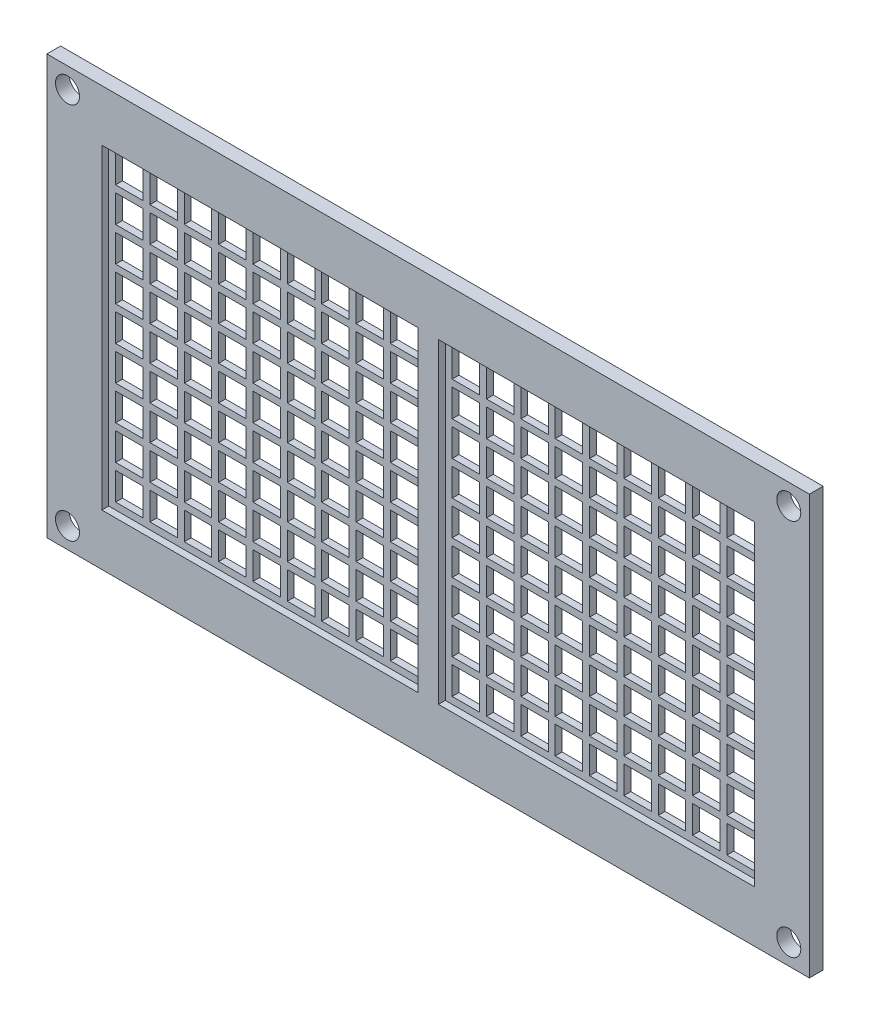
SolidWorks part; units mm, degrees
ref_plane "Front Plane" through (0, 0, 0) normal (0, 0, 1) x (1, 0, 0)
ref_plane "Top Plane" through (0, 0, 0) normal (0, 1, 0) x (1, 0, 0)
ref_plane "Right Plane" through (0, 0, 0) normal (1, 0, 0) x (0, 0, -1)
sketch "Sketch1" plane through (0, 0, 0) normal (0, 0, 1) x (1, 0, 0)
  line L1 (0, 0) -> (111, 0)
  line L2 (0, 0) -> (0, 61)
  line L3 (0, 61) -> (111, 61)
  line L4 (111, 0) -> (111, 61)
  line L5 (3, 3) -> (108, 3)
  line L6 (3, 3) -> (3, 58)
  line L7 (3, 58) -> (108, 58)
  line L8 (108, 3) -> (108, 58)
  circle A0 centre (3, 58) radius 1.75
  circle A1 centre (108, 58) radius 1.75
  circle A2 centre (108, 3) radius 1.75
  circle A3 centre (3, 3) radius 1.75
  dimension "D7" = 3.5
  dimension "D1" = 111
  dimension "D2" = 61
  dimension "D3" = 3
  dimension "D4" = 3
  dimension "D5" = 3
  dimension "D6" = 3
extrude "Boss-Extrude1" add sketch "Sketch1" along normal blind 2 contours L1 L4 L3 L2 A3 L6 A0 L7 A1 L8 A2 L5 | A3 L5 A2 L8 A1 L7 A0 L6 region at (1.2666, 30.5, 0) region at (55.5, 30.5, 0)
sketch "Sketch2" plane through (0, 0, 2) normal (0, 0, 1) x (1, 0, 0)
  line L0 (111, 0) -> (111, 61) construction
  line L1 (8, 53.5) -> (54, 53.5)
  line L2 (8, 53.5) -> (8, 7.5)
  line L3 (8, 7.5) -> (54, 7.5)
  line L4 (54, 53.5) -> (54, 7.5)
  line L5 (57, 53.5) -> (103, 53.5)
  line L6 (57, 53.5) -> (57, 7.5)
  line L7 (57, 7.5) -> (103, 7.5)
  line L8 (103, 53.5) -> (103, 7.5)
  line L9 (0, 0) -> (0, 61) construction
  line L10 (0, 61) -> (111, 61) construction
  line L11 (0, 0) -> (111, 0) construction
  dimension "D1" = 3
  dimension "D2" = 8
  dimension "D3" = 8
  dimension "D4" = 7.5
  dimension "D5" = 7.5
extrude "Cut-Extrude1" cut sketch "Sketch2" against normal blind 1
sketch "Sketch4" plane through (0, 0, 1) normal (0, 0, 1) x (1, 0, 0)
  line L0 (54, 53.5) -> (8, 53.5) construction
  line L1 (9, 52.5) -> (13, 52.5)
  line L2 (9, 52.5) -> (9, 48.5)
  line L3 (9, 48.5) -> (13, 48.5)
  line L4 (13, 52.5) -> (13, 48.5)
  line L5 (8, 53.5) -> (8, 7.5) construction
  line L6 (14, 52.5) -> (18, 52.5)
  line L7 (14, 52.5) -> (14, 48.5)
  line L8 (14, 48.5) -> (18, 48.5)
  line L9 (18, 52.5) -> (18, 48.5)
  line L10 (19, 52.5) -> (23, 52.5)
  line L11 (19, 52.5) -> (19, 48.5)
  line L12 (19, 48.5) -> (23, 48.5)
  line L13 (23, 52.5) -> (23, 48.5)
  line L14 (24, 52.5) -> (28, 52.5)
  line L15 (24, 52.5) -> (24, 48.5)
  line L16 (24, 48.5) -> (28, 48.5)
  line L17 (28, 52.5) -> (28, 48.5)
  line L18 (29, 52.5) -> (33, 52.5)
  line L19 (29, 52.5) -> (29, 48.5)
  line L20 (29, 48.5) -> (33, 48.5)
  line L21 (33, 52.5) -> (33, 48.5)
  line L22 (34, 52.5) -> (38, 52.5)
  line L23 (34, 52.5) -> (34, 48.5)
  line L24 (34, 48.5) -> (38, 48.5)
  line L25 (38, 52.5) -> (38, 48.5)
  line L26 (39, 52.5) -> (43, 52.5)
  line L27 (39, 52.5) -> (39, 48.5)
  line L28 (39, 48.5) -> (43, 48.5)
  line L29 (43, 52.5) -> (43, 48.5)
  line L30 (44, 52.5) -> (48, 52.5)
  line L31 (44, 52.5) -> (44, 48.5)
  line L32 (44, 48.5) -> (48, 48.5)
  line L33 (48, 52.5) -> (48, 48.5)
  line L34 (49, 52.5) -> (53, 52.5)
  line L35 (49, 52.5) -> (49, 48.5)
  line L36 (49, 48.5) -> (53, 48.5)
  line L37 (53, 52.5) -> (53, 48.5)
  line L38 (14, 47.5) -> (18, 47.5)
  line L39 (14, 47.5) -> (14, 43.5)
  line L40 (14, 43.5) -> (18, 43.5)
  line L41 (18, 47.5) -> (18, 43.5)
  line L42 (19, 47.5) -> (23, 47.5)
  line L43 (19, 47.5) -> (19, 43.5)
  line L44 (19, 43.5) -> (23, 43.5)
  line L45 (23, 47.5) -> (23, 43.5)
  line L46 (24, 47.5) -> (28, 47.5)
  line L47 (24, 47.5) -> (24, 43.5)
  line L48 (24, 43.5) -> (28, 43.5)
  line L49 (28, 47.5) -> (28, 43.5)
  line L50 (29, 47.5) -> (33, 47.5)
  line L51 (29, 47.5) -> (29, 43.5)
  line L52 (29, 43.5) -> (33, 43.5)
  line L53 (33, 47.5) -> (33, 43.5)
  line L54 (34, 47.5) -> (38, 47.5)
  line L55 (34, 47.5) -> (34, 43.5)
  line L56 (34, 43.5) -> (38, 43.5)
  line L57 (38, 47.5) -> (38, 43.5)
  line L58 (39, 47.5) -> (43, 47.5)
  line L59 (39, 47.5) -> (39, 43.5)
  line L60 (39, 43.5) -> (43, 43.5)
  line L61 (43, 47.5) -> (43, 43.5)
  line L62 (44, 47.5) -> (48, 47.5)
  line L63 (44, 47.5) -> (44, 43.5)
  line L64 (44, 43.5) -> (48, 43.5)
  line L65 (48, 47.5) -> (48, 43.5)
  line L66 (49, 47.5) -> (53, 47.5)
  line L67 (49, 47.5) -> (49, 43.5)
  line L68 (49, 43.5) -> (53, 43.5)
  line L69 (53, 47.5) -> (53, 43.5)
  line L70 (14, 42.5) -> (18, 42.5)
  line L71 (14, 42.5) -> (14, 38.5)
  line L72 (14, 38.5) -> (18, 38.5)
  line L73 (18, 42.5) -> (18, 38.5)
  line L74 (19, 42.5) -> (23, 42.5)
  line L75 (19, 42.5) -> (19, 38.5)
  line L76 (19, 38.5) -> (23, 38.5)
  line L77 (23, 42.5) -> (23, 38.5)
  line L78 (24, 42.5) -> (28, 42.5)
  line L79 (24, 42.5) -> (24, 38.5)
  line L80 (24, 38.5) -> (28, 38.5)
  line L81 (28, 42.5) -> (28, 38.5)
  line L82 (29, 42.5) -> (33, 42.5)
  line L83 (29, 42.5) -> (29, 38.5)
  line L84 (29, 38.5) -> (33, 38.5)
  line L85 (33, 42.5) -> (33, 38.5)
  line L86 (34, 42.5) -> (38, 42.5)
  line L87 (34, 42.5) -> (34, 38.5)
  line L88 (34, 38.5) -> (38, 38.5)
  line L89 (38, 42.5) -> (38, 38.5)
  line L90 (39, 42.5) -> (43, 42.5)
  line L91 (39, 42.5) -> (39, 38.5)
  line L92 (39, 38.5) -> (43, 38.5)
  line L93 (43, 42.5) -> (43, 38.5)
  line L94 (44, 42.5) -> (48, 42.5)
  line L95 (44, 42.5) -> (44, 38.5)
  line L96 (44, 38.5) -> (48, 38.5)
  line L97 (48, 42.5) -> (48, 38.5)
  line L98 (49, 42.5) -> (53, 42.5)
  line L99 (49, 42.5) -> (49, 38.5)
  line L100 (49, 38.5) -> (53, 38.5)
  line L101 (53, 42.5) -> (53, 38.5)
  line L102 (14, 37.5) -> (18, 37.5)
  line L103 (14, 37.5) -> (14, 33.5)
  line L104 (14, 33.5) -> (18, 33.5)
  line L105 (18, 37.5) -> (18, 33.5)
  line L106 (19, 37.5) -> (23, 37.5)
  line L107 (19, 37.5) -> (19, 33.5)
  line L108 (19, 33.5) -> (23, 33.5)
  line L109 (23, 37.5) -> (23, 33.5)
  line L110 (24, 37.5) -> (28, 37.5)
  line L111 (24, 37.5) -> (24, 33.5)
  line L112 (24, 33.5) -> (28, 33.5)
  line L113 (28, 37.5) -> (28, 33.5)
  line L114 (29, 37.5) -> (33, 37.5)
  line L115 (29, 37.5) -> (29, 33.5)
  line L116 (29, 33.5) -> (33, 33.5)
  line L117 (33, 37.5) -> (33, 33.5)
  line L118 (34, 37.5) -> (38, 37.5)
  line L119 (34, 37.5) -> (34, 33.5)
  line L120 (34, 33.5) -> (38, 33.5)
  line L121 (38, 37.5) -> (38, 33.5)
  line L122 (39, 37.5) -> (43, 37.5)
  line L123 (39, 37.5) -> (39, 33.5)
  line L124 (39, 33.5) -> (43, 33.5)
  line L125 (43, 37.5) -> (43, 33.5)
  line L126 (44, 37.5) -> (48, 37.5)
  line L127 (44, 37.5) -> (44, 33.5)
  line L128 (44, 33.5) -> (48, 33.5)
  line L129 (48, 37.5) -> (48, 33.5)
  line L130 (49, 37.5) -> (53, 37.5)
  line L131 (49, 37.5) -> (49, 33.5)
  line L132 (49, 33.5) -> (53, 33.5)
  line L133 (53, 37.5) -> (53, 33.5)
  line L134 (14, 32.5) -> (18, 32.5)
  line L135 (14, 32.5) -> (14, 28.5)
  line L136 (14, 28.5) -> (18, 28.5)
  line L137 (18, 32.5) -> (18, 28.5)
  line L138 (19, 32.5) -> (23, 32.5)
  line L139 (19, 32.5) -> (19, 28.5)
  line L140 (19, 28.5) -> (23, 28.5)
  line L141 (23, 32.5) -> (23, 28.5)
  line L142 (24, 32.5) -> (28, 32.5)
  line L143 (24, 32.5) -> (24, 28.5)
  line L144 (24, 28.5) -> (28, 28.5)
  line L145 (28, 32.5) -> (28, 28.5)
  line L146 (29, 32.5) -> (33, 32.5)
  line L147 (29, 32.5) -> (29, 28.5)
  line L148 (29, 28.5) -> (33, 28.5)
  line L149 (33, 32.5) -> (33, 28.5)
  line L150 (34, 32.5) -> (38, 32.5)
  line L151 (34, 32.5) -> (34, 28.5)
  line L152 (34, 28.5) -> (38, 28.5)
  line L153 (38, 32.5) -> (38, 28.5)
  line L154 (39, 32.5) -> (43, 32.5)
  line L155 (39, 32.5) -> (39, 28.5)
  line L156 (39, 28.5) -> (43, 28.5)
  line L157 (43, 32.5) -> (43, 28.5)
  line L158 (44, 32.5) -> (48, 32.5)
  line L159 (44, 32.5) -> (44, 28.5)
  line L160 (44, 28.5) -> (48, 28.5)
  line L161 (48, 32.5) -> (48, 28.5)
  line L162 (49, 32.5) -> (53, 32.5)
  line L163 (49, 32.5) -> (49, 28.5)
  line L164 (49, 28.5) -> (53, 28.5)
  line L165 (53, 32.5) -> (53, 28.5)
  line L166 (14, 27.5) -> (18, 27.5)
  line L167 (14, 27.5) -> (14, 23.5)
  line L168 (14, 23.5) -> (18, 23.5)
  line L169 (18, 27.5) -> (18, 23.5)
  line L170 (19, 27.5) -> (23, 27.5)
  line L171 (19, 27.5) -> (19, 23.5)
  line L172 (19, 23.5) -> (23, 23.5)
  line L173 (23, 27.5) -> (23, 23.5)
  line L174 (24, 27.5) -> (28, 27.5)
  line L175 (24, 27.5) -> (24, 23.5)
  line L176 (24, 23.5) -> (28, 23.5)
  line L177 (28, 27.5) -> (28, 23.5)
  line L178 (29, 27.5) -> (33, 27.5)
  line L179 (29, 27.5) -> (29, 23.5)
  line L180 (29, 23.5) -> (33, 23.5)
  line L181 (33, 27.5) -> (33, 23.5)
  line L182 (34, 27.5) -> (38, 27.5)
  line L183 (34, 27.5) -> (34, 23.5)
  line L184 (34, 23.5) -> (38, 23.5)
  line L185 (38, 27.5) -> (38, 23.5)
  line L186 (39, 27.5) -> (43, 27.5)
  line L187 (39, 27.5) -> (39, 23.5)
  line L188 (39, 23.5) -> (43, 23.5)
  line L189 (43, 27.5) -> (43, 23.5)
  line L190 (44, 27.5) -> (48, 27.5)
  line L191 (44, 27.5) -> (44, 23.5)
  line L192 (44, 23.5) -> (48, 23.5)
  line L193 (48, 27.5) -> (48, 23.5)
  line L194 (49, 27.5) -> (53, 27.5)
  line L195 (49, 27.5) -> (49, 23.5)
  line L196 (49, 23.5) -> (53, 23.5)
  line L197 (53, 27.5) -> (53, 23.5)
  line L198 (14, 22.5) -> (18, 22.5)
  line L199 (14, 22.5) -> (14, 18.5)
  line L200 (14, 18.5) -> (18, 18.5)
  line L201 (18, 22.5) -> (18, 18.5)
  line L202 (19, 22.5) -> (23, 22.5)
  line L203 (19, 22.5) -> (19, 18.5)
  line L204 (19, 18.5) -> (23, 18.5)
  line L205 (23, 22.5) -> (23, 18.5)
  line L206 (24, 22.5) -> (28, 22.5)
  line L207 (24, 22.5) -> (24, 18.5)
  line L208 (24, 18.5) -> (28, 18.5)
  line L209 (28, 22.5) -> (28, 18.5)
  line L210 (29, 22.5) -> (33, 22.5)
  line L211 (29, 22.5) -> (29, 18.5)
  line L212 (29, 18.5) -> (33, 18.5)
  line L213 (33, 22.5) -> (33, 18.5)
  line L214 (34, 22.5) -> (38, 22.5)
  line L215 (34, 22.5) -> (34, 18.5)
  line L216 (34, 18.5) -> (38, 18.5)
  line L217 (38, 22.5) -> (38, 18.5)
  line L218 (39, 22.5) -> (43, 22.5)
  line L219 (39, 22.5) -> (39, 18.5)
  line L220 (39, 18.5) -> (43, 18.5)
  line L221 (43, 22.5) -> (43, 18.5)
  line L222 (44, 22.5) -> (48, 22.5)
  line L223 (44, 22.5) -> (44, 18.5)
  line L224 (44, 18.5) -> (48, 18.5)
  line L225 (48, 22.5) -> (48, 18.5)
  line L226 (49, 22.5) -> (53, 22.5)
  line L227 (49, 22.5) -> (49, 18.5)
  line L228 (49, 18.5) -> (53, 18.5)
  line L229 (53, 22.5) -> (53, 18.5)
  line L230 (14, 17.5) -> (18, 17.5)
  line L231 (14, 17.5) -> (14, 13.5)
  line L232 (14, 13.5) -> (18, 13.5)
  line L233 (18, 17.5) -> (18, 13.5)
  line L234 (19, 17.5) -> (23, 17.5)
  line L235 (19, 17.5) -> (19, 13.5)
  line L236 (19, 13.5) -> (23, 13.5)
  line L237 (23, 17.5) -> (23, 13.5)
  line L238 (24, 17.5) -> (28, 17.5)
  line L239 (24, 17.5) -> (24, 13.5)
  line L240 (24, 13.5) -> (28, 13.5)
  line L241 (28, 17.5) -> (28, 13.5)
  line L242 (29, 17.5) -> (33, 17.5)
  line L243 (29, 17.5) -> (29, 13.5)
  line L244 (29, 13.5) -> (33, 13.5)
  line L245 (33, 17.5) -> (33, 13.5)
  line L246 (34, 17.5) -> (38, 17.5)
  line L247 (34, 17.5) -> (34, 13.5)
  line L248 (34, 13.5) -> (38, 13.5)
  line L249 (38, 17.5) -> (38, 13.5)
  line L250 (39, 17.5) -> (43, 17.5)
  line L251 (39, 17.5) -> (39, 13.5)
  line L252 (39, 13.5) -> (43, 13.5)
  line L253 (43, 17.5) -> (43, 13.5)
  line L254 (44, 17.5) -> (48, 17.5)
  line L255 (44, 17.5) -> (44, 13.5)
  line L256 (44, 13.5) -> (48, 13.5)
  line L257 (48, 17.5) -> (48, 13.5)
  line L258 (49, 17.5) -> (53, 17.5)
  line L259 (49, 17.5) -> (49, 13.5)
  line L260 (49, 13.5) -> (53, 13.5)
  line L261 (53, 17.5) -> (53, 13.5)
  line L262 (14, 12.5) -> (18, 12.5)
  line L263 (14, 12.5) -> (14, 8.5)
  line L264 (14, 8.5) -> (18, 8.5)
  line L265 (18, 12.5) -> (18, 8.5)
  line L266 (19, 12.5) -> (23, 12.5)
  line L267 (19, 12.5) -> (19, 8.5)
  line L268 (19, 8.5) -> (23, 8.5)
  line L269 (23, 12.5) -> (23, 8.5)
  line L270 (24, 12.5) -> (28, 12.5)
  line L271 (24, 12.5) -> (24, 8.5)
  line L272 (24, 8.5) -> (28, 8.5)
  line L273 (28, 12.5) -> (28, 8.5)
  line L274 (29, 12.5) -> (33, 12.5)
  line L275 (29, 12.5) -> (29, 8.5)
  line L276 (29, 8.5) -> (33, 8.5)
  line L277 (33, 12.5) -> (33, 8.5)
  line L278 (34, 12.5) -> (38, 12.5)
  line L279 (34, 12.5) -> (34, 8.5)
  line L280 (34, 8.5) -> (38, 8.5)
  line L281 (38, 12.5) -> (38, 8.5)
  line L282 (39, 12.5) -> (43, 12.5)
  line L283 (39, 12.5) -> (39, 8.5)
  line L284 (39, 8.5) -> (43, 8.5)
  line L285 (43, 12.5) -> (43, 8.5)
  line L286 (44, 12.5) -> (48, 12.5)
  line L287 (44, 12.5) -> (44, 8.5)
  line L288 (44, 8.5) -> (48, 8.5)
  line L289 (48, 12.5) -> (48, 8.5)
  line L290 (49, 12.5) -> (53, 12.5)
  line L291 (49, 12.5) -> (49, 8.5)
  line L292 (49, 8.5) -> (53, 8.5)
  line L293 (53, 12.5) -> (53, 8.5)
  line L294 (9, 47.5) -> (13, 47.5)
  line L295 (9, 47.5) -> (9, 43.5)
  line L296 (9, 43.5) -> (13, 43.5)
  line L297 (13, 47.5) -> (13, 43.5)
  line L298 (9, 42.5) -> (13, 42.5)
  line L299 (9, 42.5) -> (9, 38.5)
  line L300 (9, 38.5) -> (13, 38.5)
  line L301 (13, 42.5) -> (13, 38.5)
  line L302 (9, 37.5) -> (13, 37.5)
  line L303 (9, 37.5) -> (9, 33.5)
  line L304 (9, 33.5) -> (13, 33.5)
  line L305 (13, 37.5) -> (13, 33.5)
  line L306 (9, 32.5) -> (13, 32.5)
  line L307 (9, 32.5) -> (9, 28.5)
  line L308 (9, 28.5) -> (13, 28.5)
  line L309 (13, 32.5) -> (13, 28.5)
  line L310 (9, 27.5) -> (13, 27.5)
  line L311 (9, 27.5) -> (9, 23.5)
  line L312 (9, 23.5) -> (13, 23.5)
  line L313 (13, 27.5) -> (13, 23.5)
  line L314 (9, 22.5) -> (13, 22.5)
  line L315 (9, 22.5) -> (9, 18.5)
  line L316 (9, 18.5) -> (13, 18.5)
  line L317 (13, 22.5) -> (13, 18.5)
  line L318 (9, 17.5) -> (13, 17.5)
  line L319 (9, 17.5) -> (9, 13.5)
  line L320 (9, 13.5) -> (13, 13.5)
  line L321 (13, 17.5) -> (13, 13.5)
  line L322 (9, 12.5) -> (13, 12.5)
  line L323 (9, 12.5) -> (9, 8.5)
  line L324 (9, 8.5) -> (13, 8.5)
  line L325 (13, 12.5) -> (13, 8.5)
  dimension "D1" = 1
  dimension "D2" = 1
  dimension "D3" = 4
  dimension "D4" = 4
  dimension "D5" = 9
  dimension "D6" = 9
extrude "Cut-Extrude2" cut sketch "Sketch4" against normal through all
sketch "Sketch5" plane through (0, 0, 0) normal (0, 0, 1) x (1, 0, 0)
  line L1 (58, 52.5) -> (62, 52.5)
  line L2 (58, 52.5) -> (58, 48.5)
  line L3 (58, 48.5) -> (62, 48.5)
  line L4 (62, 52.5) -> (62, 48.5)
  line L6 (63, 52.5) -> (67, 52.5)
  line L7 (63, 52.5) -> (63, 48.5)
  line L8 (63, 48.5) -> (67, 48.5)
  line L9 (67, 52.5) -> (67, 48.5)
  line L10 (68, 52.5) -> (72, 52.5)
  line L11 (68, 52.5) -> (68, 48.5)
  line L12 (68, 48.5) -> (72, 48.5)
  line L13 (72, 52.5) -> (72, 48.5)
  line L14 (73, 52.5) -> (77, 52.5)
  line L15 (73, 52.5) -> (73, 48.5)
  line L16 (73, 48.5) -> (77, 48.5)
  line L17 (77, 52.5) -> (77, 48.5)
  line L18 (78, 52.5) -> (82, 52.5)
  line L19 (78, 52.5) -> (78, 48.5)
  line L20 (78, 48.5) -> (82, 48.5)
  line L21 (82, 52.5) -> (82, 48.5)
  line L22 (83, 52.5) -> (87, 52.5)
  line L23 (83, 52.5) -> (83, 48.5)
  line L24 (83, 48.5) -> (87, 48.5)
  line L25 (87, 52.5) -> (87, 48.5)
  line L26 (88, 52.5) -> (92, 52.5)
  line L27 (88, 52.5) -> (88, 48.5)
  line L28 (88, 48.5) -> (92, 48.5)
  line L29 (92, 52.5) -> (92, 48.5)
  line L30 (93, 52.5) -> (97, 52.5)
  line L31 (93, 52.5) -> (93, 48.5)
  line L32 (93, 48.5) -> (97, 48.5)
  line L33 (97, 52.5) -> (97, 48.5)
  line L34 (98, 52.5) -> (102, 52.5)
  line L35 (98, 52.5) -> (98, 48.5)
  line L36 (98, 48.5) -> (102, 48.5)
  line L37 (102, 52.5) -> (102, 48.5)
  line L38 (63, 47.5) -> (67, 47.5)
  line L39 (63, 47.5) -> (63, 43.5)
  line L40 (63, 43.5) -> (67, 43.5)
  line L41 (67, 47.5) -> (67, 43.5)
  line L42 (68, 47.5) -> (72, 47.5)
  line L43 (68, 47.5) -> (68, 43.5)
  line L44 (68, 43.5) -> (72, 43.5)
  line L45 (72, 47.5) -> (72, 43.5)
  line L46 (73, 47.5) -> (77, 47.5)
  line L47 (73, 47.5) -> (73, 43.5)
  line L48 (73, 43.5) -> (77, 43.5)
  line L49 (77, 47.5) -> (77, 43.5)
  line L50 (78, 47.5) -> (82, 47.5)
  line L51 (78, 47.5) -> (78, 43.5)
  line L52 (78, 43.5) -> (82, 43.5)
  line L53 (82, 47.5) -> (82, 43.5)
  line L54 (83, 47.5) -> (87, 47.5)
  line L55 (83, 47.5) -> (83, 43.5)
  line L56 (83, 43.5) -> (87, 43.5)
  line L57 (87, 47.5) -> (87, 43.5)
  line L58 (88, 47.5) -> (92, 47.5)
  line L59 (88, 47.5) -> (88, 43.5)
  line L60 (88, 43.5) -> (92, 43.5)
  line L61 (92, 47.5) -> (92, 43.5)
  line L62 (93, 47.5) -> (97, 47.5)
  line L63 (93, 47.5) -> (93, 43.5)
  line L64 (93, 43.5) -> (97, 43.5)
  line L65 (97, 47.5) -> (97, 43.5)
  line L66 (98, 47.5) -> (102, 47.5)
  line L67 (98, 47.5) -> (98, 43.5)
  line L68 (98, 43.5) -> (102, 43.5)
  line L69 (102, 47.5) -> (102, 43.5)
  line L70 (63, 42.5) -> (67, 42.5)
  line L71 (63, 42.5) -> (63, 38.5)
  line L72 (63, 38.5) -> (67, 38.5)
  line L73 (67, 42.5) -> (67, 38.5)
  line L74 (68, 42.5) -> (72, 42.5)
  line L75 (68, 42.5) -> (68, 38.5)
  line L76 (68, 38.5) -> (72, 38.5)
  line L77 (72, 42.5) -> (72, 38.5)
  line L78 (73, 42.5) -> (77, 42.5)
  line L79 (73, 42.5) -> (73, 38.5)
  line L80 (73, 38.5) -> (77, 38.5)
  line L81 (77, 42.5) -> (77, 38.5)
  line L82 (78, 42.5) -> (82, 42.5)
  line L83 (78, 42.5) -> (78, 38.5)
  line L84 (78, 38.5) -> (82, 38.5)
  line L85 (82, 42.5) -> (82, 38.5)
  line L86 (83, 42.5) -> (87, 42.5)
  line L87 (83, 42.5) -> (83, 38.5)
  line L88 (83, 38.5) -> (87, 38.5)
  line L89 (87, 42.5) -> (87, 38.5)
  line L90 (88, 42.5) -> (92, 42.5)
  line L91 (88, 42.5) -> (88, 38.5)
  line L92 (88, 38.5) -> (92, 38.5)
  line L93 (92, 42.5) -> (92, 38.5)
  line L94 (93, 42.5) -> (97, 42.5)
  line L95 (93, 42.5) -> (93, 38.5)
  line L96 (93, 38.5) -> (97, 38.5)
  line L97 (97, 42.5) -> (97, 38.5)
  line L98 (98, 42.5) -> (102, 42.5)
  line L99 (98, 42.5) -> (98, 38.5)
  line L100 (98, 38.5) -> (102, 38.5)
  line L101 (102, 42.5) -> (102, 38.5)
  line L102 (63, 37.5) -> (67, 37.5)
  line L103 (63, 37.5) -> (63, 33.5)
  line L104 (63, 33.5) -> (67, 33.5)
  line L105 (67, 37.5) -> (67, 33.5)
  line L106 (68, 37.5) -> (72, 37.5)
  line L107 (68, 37.5) -> (68, 33.5)
  line L108 (68, 33.5) -> (72, 33.5)
  line L109 (72, 37.5) -> (72, 33.5)
  line L110 (73, 37.5) -> (77, 37.5)
  line L111 (73, 37.5) -> (73, 33.5)
  line L112 (73, 33.5) -> (77, 33.5)
  line L113 (77, 37.5) -> (77, 33.5)
  line L114 (78, 37.5) -> (82, 37.5)
  line L115 (78, 37.5) -> (78, 33.5)
  line L116 (78, 33.5) -> (82, 33.5)
  line L117 (82, 37.5) -> (82, 33.5)
  line L118 (83, 37.5) -> (87, 37.5)
  line L119 (83, 37.5) -> (83, 33.5)
  line L120 (83, 33.5) -> (87, 33.5)
  line L121 (87, 37.5) -> (87, 33.5)
  line L122 (88, 37.5) -> (92, 37.5)
  line L123 (88, 37.5) -> (88, 33.5)
  line L124 (88, 33.5) -> (92, 33.5)
  line L125 (92, 37.5) -> (92, 33.5)
  line L126 (93, 37.5) -> (97, 37.5)
  line L127 (93, 37.5) -> (93, 33.5)
  line L128 (93, 33.5) -> (97, 33.5)
  line L129 (97, 37.5) -> (97, 33.5)
  line L130 (98, 37.5) -> (102, 37.5)
  line L131 (98, 37.5) -> (98, 33.5)
  line L132 (98, 33.5) -> (102, 33.5)
  line L133 (102, 37.5) -> (102, 33.5)
  line L134 (63, 32.5) -> (67, 32.5)
  line L135 (63, 32.5) -> (63, 28.5)
  line L136 (63, 28.5) -> (67, 28.5)
  line L137 (67, 32.5) -> (67, 28.5)
  line L138 (68, 32.5) -> (72, 32.5)
  line L139 (68, 32.5) -> (68, 28.5)
  line L140 (68, 28.5) -> (72, 28.5)
  line L141 (72, 32.5) -> (72, 28.5)
  line L142 (73, 32.5) -> (77, 32.5)
  line L143 (73, 32.5) -> (73, 28.5)
  line L144 (73, 28.5) -> (77, 28.5)
  line L145 (77, 32.5) -> (77, 28.5)
  line L146 (78, 32.5) -> (82, 32.5)
  line L147 (78, 32.5) -> (78, 28.5)
  line L148 (78, 28.5) -> (82, 28.5)
  line L149 (82, 32.5) -> (82, 28.5)
  line L150 (83, 32.5) -> (87, 32.5)
  line L151 (83, 32.5) -> (83, 28.5)
  line L152 (83, 28.5) -> (87, 28.5)
  line L153 (87, 32.5) -> (87, 28.5)
  line L154 (88, 32.5) -> (92, 32.5)
  line L155 (88, 32.5) -> (88, 28.5)
  line L156 (88, 28.5) -> (92, 28.5)
  line L157 (92, 32.5) -> (92, 28.5)
  line L158 (93, 32.5) -> (97, 32.5)
  line L159 (93, 32.5) -> (93, 28.5)
  line L160 (93, 28.5) -> (97, 28.5)
  line L161 (97, 32.5) -> (97, 28.5)
  line L162 (98, 32.5) -> (102, 32.5)
  line L163 (98, 32.5) -> (98, 28.5)
  line L164 (98, 28.5) -> (102, 28.5)
  line L165 (102, 32.5) -> (102, 28.5)
  line L166 (63, 27.5) -> (67, 27.5)
  line L167 (63, 27.5) -> (63, 23.5)
  line L168 (63, 23.5) -> (67, 23.5)
  line L169 (67, 27.5) -> (67, 23.5)
  line L170 (68, 27.5) -> (72, 27.5)
  line L171 (68, 27.5) -> (68, 23.5)
  line L172 (68, 23.5) -> (72, 23.5)
  line L173 (72, 27.5) -> (72, 23.5)
  line L174 (73, 27.5) -> (77, 27.5)
  line L175 (73, 27.5) -> (73, 23.5)
  line L176 (73, 23.5) -> (77, 23.5)
  line L177 (77, 27.5) -> (77, 23.5)
  line L178 (78, 27.5) -> (82, 27.5)
  line L179 (78, 27.5) -> (78, 23.5)
  line L180 (78, 23.5) -> (82, 23.5)
  line L181 (82, 27.5) -> (82, 23.5)
  line L182 (83, 27.5) -> (87, 27.5)
  line L183 (83, 27.5) -> (83, 23.5)
  line L184 (83, 23.5) -> (87, 23.5)
  line L185 (87, 27.5) -> (87, 23.5)
  line L186 (88, 27.5) -> (92, 27.5)
  line L187 (88, 27.5) -> (88, 23.5)
  line L188 (88, 23.5) -> (92, 23.5)
  line L189 (92, 27.5) -> (92, 23.5)
  line L190 (93, 27.5) -> (97, 27.5)
  line L191 (93, 27.5) -> (93, 23.5)
  line L192 (93, 23.5) -> (97, 23.5)
  line L193 (97, 27.5) -> (97, 23.5)
  line L194 (98, 27.5) -> (102, 27.5)
  line L195 (98, 27.5) -> (98, 23.5)
  line L196 (98, 23.5) -> (102, 23.5)
  line L197 (102, 27.5) -> (102, 23.5)
  line L198 (63, 22.5) -> (67, 22.5)
  line L199 (63, 22.5) -> (63, 18.5)
  line L200 (63, 18.5) -> (67, 18.5)
  line L201 (67, 22.5) -> (67, 18.5)
  line L202 (68, 22.5) -> (72, 22.5)
  line L203 (68, 22.5) -> (68, 18.5)
  line L204 (68, 18.5) -> (72, 18.5)
  line L205 (72, 22.5) -> (72, 18.5)
  line L206 (73, 22.5) -> (77, 22.5)
  line L207 (73, 22.5) -> (73, 18.5)
  line L208 (73, 18.5) -> (77, 18.5)
  line L209 (77, 22.5) -> (77, 18.5)
  line L210 (78, 22.5) -> (82, 22.5)
  line L211 (78, 22.5) -> (78, 18.5)
  line L212 (78, 18.5) -> (82, 18.5)
  line L213 (82, 22.5) -> (82, 18.5)
  line L214 (83, 22.5) -> (87, 22.5)
  line L215 (83, 22.5) -> (83, 18.5)
  line L216 (83, 18.5) -> (87, 18.5)
  line L217 (87, 22.5) -> (87, 18.5)
  line L218 (88, 22.5) -> (92, 22.5)
  line L219 (88, 22.5) -> (88, 18.5)
  line L220 (88, 18.5) -> (92, 18.5)
  line L221 (92, 22.5) -> (92, 18.5)
  line L222 (93, 22.5) -> (97, 22.5)
  line L223 (93, 22.5) -> (93, 18.5)
  line L224 (93, 18.5) -> (97, 18.5)
  line L225 (97, 22.5) -> (97, 18.5)
  line L226 (98, 22.5) -> (102, 22.5)
  line L227 (98, 22.5) -> (98, 18.5)
  line L228 (98, 18.5) -> (102, 18.5)
  line L229 (102, 22.5) -> (102, 18.5)
  line L230 (63, 17.5) -> (67, 17.5)
  line L231 (63, 17.5) -> (63, 13.5)
  line L232 (63, 13.5) -> (67, 13.5)
  line L233 (67, 17.5) -> (67, 13.5)
  line L234 (68, 17.5) -> (72, 17.5)
  line L235 (68, 17.5) -> (68, 13.5)
  line L236 (68, 13.5) -> (72, 13.5)
  line L237 (72, 17.5) -> (72, 13.5)
  line L238 (73, 17.5) -> (77, 17.5)
  line L239 (73, 17.5) -> (73, 13.5)
  line L240 (73, 13.5) -> (77, 13.5)
  line L241 (77, 17.5) -> (77, 13.5)
  line L242 (78, 17.5) -> (82, 17.5)
  line L243 (78, 17.5) -> (78, 13.5)
  line L244 (78, 13.5) -> (82, 13.5)
  line L245 (82, 17.5) -> (82, 13.5)
  line L246 (83, 17.5) -> (87, 17.5)
  line L247 (83, 17.5) -> (83, 13.5)
  line L248 (83, 13.5) -> (87, 13.5)
  line L249 (87, 17.5) -> (87, 13.5)
  line L250 (88, 17.5) -> (92, 17.5)
  line L251 (88, 17.5) -> (88, 13.5)
  line L252 (88, 13.5) -> (92, 13.5)
  line L253 (92, 17.5) -> (92, 13.5)
  line L254 (93, 17.5) -> (97, 17.5)
  line L255 (93, 17.5) -> (93, 13.5)
  line L256 (93, 13.5) -> (97, 13.5)
  line L257 (97, 17.5) -> (97, 13.5)
  line L258 (98, 17.5) -> (102, 17.5)
  line L259 (98, 17.5) -> (98, 13.5)
  line L260 (98, 13.5) -> (102, 13.5)
  line L261 (102, 17.5) -> (102, 13.5)
  line L262 (63, 12.5) -> (67, 12.5)
  line L263 (63, 12.5) -> (63, 8.5)
  line L264 (63, 8.5) -> (67, 8.5)
  line L265 (67, 12.5) -> (67, 8.5)
  line L266 (68, 12.5) -> (72, 12.5)
  line L267 (68, 12.5) -> (68, 8.5)
  line L268 (68, 8.5) -> (72, 8.5)
  line L269 (72, 12.5) -> (72, 8.5)
  line L270 (73, 12.5) -> (77, 12.5)
  line L271 (73, 12.5) -> (73, 8.5)
  line L272 (73, 8.5) -> (77, 8.5)
  line L273 (77, 12.5) -> (77, 8.5)
  line L274 (78, 12.5) -> (82, 12.5)
  line L275 (78, 12.5) -> (78, 8.5)
  line L276 (78, 8.5) -> (82, 8.5)
  line L277 (82, 12.5) -> (82, 8.5)
  line L278 (83, 12.5) -> (87, 12.5)
  line L279 (83, 12.5) -> (83, 8.5)
  line L280 (83, 8.5) -> (87, 8.5)
  line L281 (87, 12.5) -> (87, 8.5)
  line L282 (88, 12.5) -> (92, 12.5)
  line L283 (88, 12.5) -> (88, 8.5)
  line L284 (88, 8.5) -> (92, 8.5)
  line L285 (92, 12.5) -> (92, 8.5)
  line L286 (93, 12.5) -> (97, 12.5)
  line L287 (93, 12.5) -> (93, 8.5)
  line L288 (93, 8.5) -> (97, 8.5)
  line L289 (97, 12.5) -> (97, 8.5)
  line L290 (98, 12.5) -> (102, 12.5)
  line L291 (98, 12.5) -> (98, 8.5)
  line L292 (98, 8.5) -> (102, 8.5)
  line L293 (102, 12.5) -> (102, 8.5)
  line L294 (58, 47.5) -> (62, 47.5)
  line L295 (58, 47.5) -> (58, 43.5)
  line L296 (58, 43.5) -> (62, 43.5)
  line L297 (62, 47.5) -> (62, 43.5)
  line L298 (58, 42.5) -> (62, 42.5)
  line L299 (58, 42.5) -> (58, 38.5)
  line L300 (58, 38.5) -> (62, 38.5)
  line L301 (62, 42.5) -> (62, 38.5)
  line L302 (58, 37.5) -> (62, 37.5)
  line L303 (58, 37.5) -> (58, 33.5)
  line L304 (58, 33.5) -> (62, 33.5)
  line L305 (62, 37.5) -> (62, 33.5)
  line L306 (58, 32.5) -> (62, 32.5)
  line L307 (58, 32.5) -> (58, 28.5)
  line L308 (58, 28.5) -> (62, 28.5)
  line L309 (62, 32.5) -> (62, 28.5)
  line L310 (58, 27.5) -> (62, 27.5)
  line L311 (58, 27.5) -> (58, 23.5)
  line L312 (58, 23.5) -> (62, 23.5)
  line L313 (62, 27.5) -> (62, 23.5)
  line L314 (58, 22.5) -> (62, 22.5)
  line L315 (58, 22.5) -> (58, 18.5)
  line L316 (58, 18.5) -> (62, 18.5)
  line L317 (62, 22.5) -> (62, 18.5)
  line L318 (58, 17.5) -> (62, 17.5)
  line L319 (58, 17.5) -> (58, 13.5)
  line L320 (58, 13.5) -> (62, 13.5)
  line L321 (62, 17.5) -> (62, 13.5)
  line L322 (58, 12.5) -> (62, 12.5)
  line L323 (58, 12.5) -> (58, 8.5)
  line L324 (58, 8.5) -> (62, 8.5)
  line L325 (62, 12.5) -> (62, 8.5)
  line L326 (57, 53.5) -> (57, 7.5) construction
  line L327 (103, 53.5) -> (57, 53.5) construction
  dimension "D1" = 1
  dimension "D2" = 1
  dimension "D3" = 4
  dimension "D4" = 4
  dimension "D5" = 9
  dimension "D6" = 9
extrude "Cut-Extrude5" cut sketch "Sketch5" along normal through all
